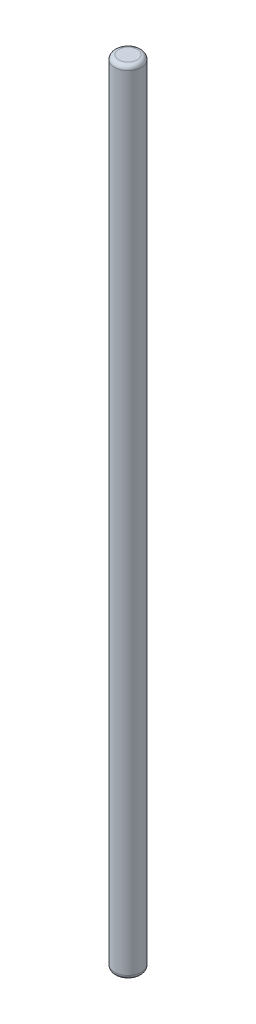
SolidWorks part; units mm, degrees
material "1023 Carbon Steel Sheet (SS)"
ref_plane "Front Plane" through (0, 0, 0) normal (0, 0, 1) x (1, 0, 0)
ref_plane "Top Plane" through (0, 0, 0) normal (0, 1, 0) x (1, 0, 0)
ref_plane "Right Plane" through (0, 0, 0) normal (1, 0, 0) x (0, 0, -1)
sketch "Sketch1" plane through (0, 0, 0) normal (0, 1, 0) x (1, 0, 0)
  circle A0 centre (0, 0) radius 2.3813
  dimension "D1" = 4.7625
extrude "Boss-Extrude1" add sketch "Sketch1" along normal blind 139.7
fillet "Fillet1" radius 0.762 2 edges at (0, 0, 2.3813) (0, 139.7, 2.3813)
